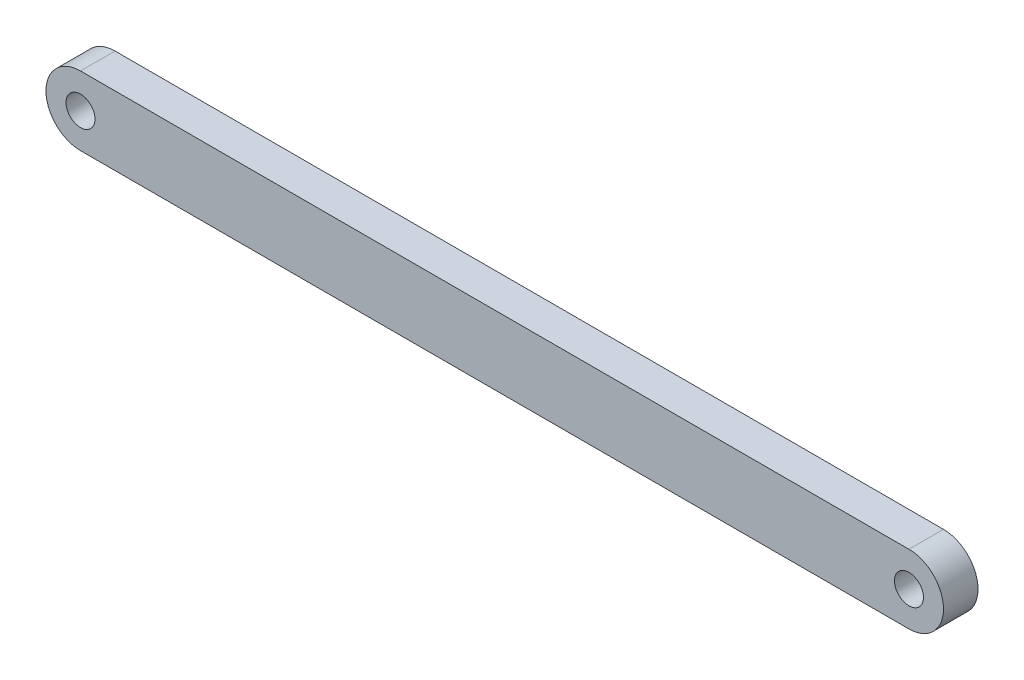
SolidWorks part; units mm, degrees
ref_plane "Front Plane" through (0, 0, 0) normal (0, 0, 1) x (1, 0, 0)
ref_plane "Top Plane" through (0, 0, 0) normal (0, 1, 0) x (1, 0, 0)
ref_plane "Right Plane" through (0, 0, 0) normal (1, 0, 0) x (0, 0, -1)
sketch "Sketch1" plane through (0, 0, 0) normal (0, 0, 1) x (1, 0, 0)
  line L0 (-60, 0) -> (60, 0)
  line L1 (0, -5.5) -> (0, 5.5) construction
  line L2 (-60, 5) -> (60, 5)
  line L3 (-60, -5) -> (60, -5)
  circle A0 centre (60, 0) radius 5
  circle A1 centre (-60, 0) radius 5
  point P4 (0, 0)
extrude "Boss-Extrude1" add sketch "Sketch1" along normal mid plane 6 contours A1 | L2 A1 L0 A0 | L0 A1 L3 A0 | A0 region at (0, 2.5265, 0) region at (-56.5645, -3.4355, 0) region at (0, -2.5265, 0) region at (56.5645, 3.4355, 0)
ref_axis "Axis1" through (60, 0, 13.7762) along (0, 0, -1)
ref_axis "Axis2" through (-60, 0, 13.2784) along (0, 0, -1)
sketch "Sketch2" plane through (0, 0, 3) normal (0, 0, 1) x (1, 0, 0)
  line L1 (-78.8175, 27.6715) -> (77.1102, 27.6715)
  line L2 (-78.8175, 27.6715) -> (-78.8175, -27.5292)
  line L3 (-78.8175, -27.5292) -> (77.1102, -27.5292)
  line L4 (77.1102, 27.6715) -> (77.1102, -27.5292)
extrude "Cut-Extrude1" cut sketch "Sketch2" against normal blind 1
sketch "Sketch3" plane through (0, 0, -3) normal (0, 0, -1) x (-1, 0, 0)
  circle A0 centre (-60, 0) radius 2.1
  circle A1 centre (60, 0) radius 2.1
extrude "Cut-Extrude2" cut sketch "Sketch3" against normal through all
